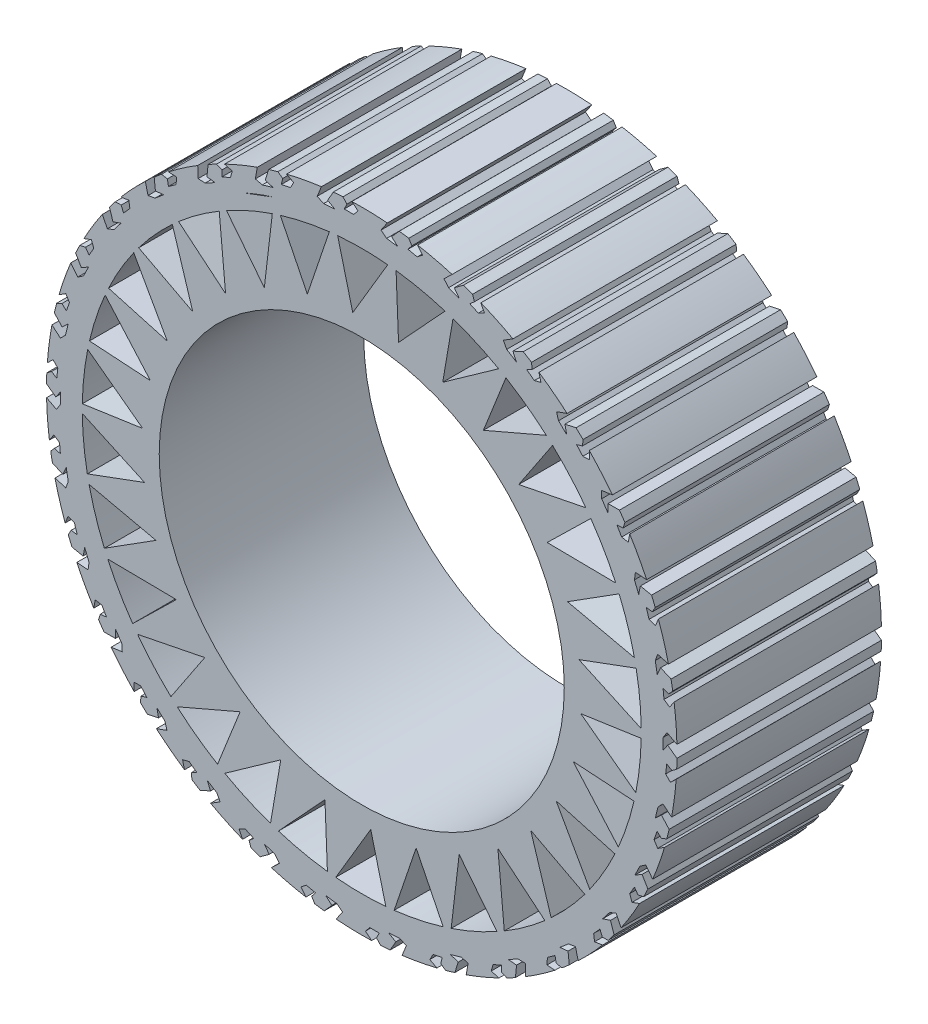
SolidWorks part; units mm, degrees
ref_plane "Front Plane" through (0, 0, 0) normal (0, 0, 1) x (1, 0, 0)
ref_plane "Top Plane" through (0, 0, 0) normal (0, 1, 0) x (1, 0, 0)
ref_plane "Right Plane" through (0, 0, 0) normal (1, 0, 0) x (0, 0, -1)
sketch "Sketch1" plane through (0, 0, 0) normal (0, 0, 1) x (1, 0, 0)
  line L0 (154.9481, 259.0555) -> (145.2899, 265.0606)
  line L1 (-169.385, 140.3878) -> (-194.3847, 220.5688)
  line L2 (-194.8718, 102.1028) -> (-235.9957, 175.334)
  line L3 (-194.8718, 102.1028) -> (-267.2926, 122.4363)
  line L4 (-169.385, 140.3878) -> (-235.9957, 175.334)
  line L5 (-136.4953, 172.5371) -> (-144.278, 256.1637)
  line L6 (-136.4953, 172.5371) -> (-194.3847, 220.5688)
  line L7 (-97.6401, 197.1457) -> (-87.8658, 280.563)
  line L8 (-97.6401, 197.1457) -> (-144.278, 256.1637)
  line L9 (-54.5175, 213.1381) -> (-27.6134, 292.7004)
  line L10 (-54.5175, 213.1381) -> (-87.8658, 280.563)
  line L11 (-9.0123, 219.8153) -> (33.8459, 292.0453)
  line L12 (-9.0123, 219.8153) -> (-27.6134, 292.7004)
  line L13 (36.8869, 216.8856) -> (93.8259, 278.6265)
  line L14 (36.8869, 216.8856) -> (33.8459, 292.0453)
  line L15 (81.1738, 204.4769) -> (149.7053, 253.0303)
  line L16 (81.1738, 204.4769) -> (93.8259, 278.6265)
  line L17 (121.9131, 183.1316) -> (199.0418, 216.3755)
  line L18 (121.9131, 183.1316) -> (149.7053, 253.0303)
  line L19 (157.3243, 153.7826) -> (239.6793, 170.2641)
  line L20 (157.3243, 153.7826) -> (199.0418, 216.3755)
  line L21 (185.8595, 117.7125) -> (269.8416, 116.7113)
  line L22 (185.8595, 117.7125) -> (239.6793, 170.2641)
  line L23 (206.2719, 76.4978) -> (288.2105, 58.0576)
  line L24 (206.2719, 76.4978) -> (269.8416, 116.7113)
  line L25 (217.6691, 31.9398) -> (293.9833, -3.1334)
  line L26 (217.6691, 31.9398) -> (288.2105, 58.0576)
  line L27 (219.5532, -14.0141) -> (286.9076, -64.1875)
  line L28 (219.5532, -14.0141) -> (293.9833, -3.1334)
  line L29 (211.8417, -59.3555) -> (267.2926, -122.4363)
  line L30 (211.8417, -59.3555) -> (286.9076, -64.1875)
  line L31 (194.8718, -102.1028) -> (235.9957, -175.334)
  line L32 (194.8718, -102.1028) -> (267.2926, -122.4363)
  line L33 (169.385, -140.3878) -> (194.3847, -220.5688)
  line L34 (169.385, -140.3878) -> (235.9957, -175.334)
  line L35 (136.4953, -172.5371) -> (144.278, -256.1637)
  line L36 (136.4953, -172.5371) -> (194.3847, -220.5688)
  line L37 (97.6401, -197.1457) -> (87.8658, -280.563)
  line L38 (97.6401, -197.1457) -> (144.278, -256.1637)
  line L39 (54.5175, -213.1381) -> (27.6134, -292.7004)
  line L40 (54.5175, -213.1381) -> (87.8658, -280.563)
  line L41 (9.0123, -219.8153) -> (-33.8459, -292.0453)
  line L42 (9.0123, -219.8153) -> (27.6134, -292.7004)
  line L43 (-36.8869, -216.8856) -> (-93.8259, -278.6265)
  line L44 (-36.8869, -216.8856) -> (-33.8459, -292.0453)
  line L45 (-81.1738, -204.4769) -> (-149.7053, -253.0303)
  line L46 (-81.1738, -204.4769) -> (-93.8259, -278.6265)
  line L47 (-121.9131, -183.1316) -> (-199.0418, -216.3755)
  line L48 (-121.9131, -183.1316) -> (-149.7053, -253.0303)
  line L49 (-157.3243, -153.7826) -> (-239.6793, -170.2641)
  line L50 (-157.3243, -153.7826) -> (-199.0418, -216.3755)
  line L51 (-185.8595, -117.7125) -> (-269.8416, -116.7113)
  line L52 (-185.8595, -117.7125) -> (-239.6793, -170.2641)
  line L53 (-206.2719, -76.4978) -> (-288.2105, -58.0576)
  line L54 (-206.2719, -76.4978) -> (-269.8416, -116.7113)
  line L55 (-217.6691, -31.9398) -> (-293.9833, 3.1334)
  line L56 (-217.6691, -31.9398) -> (-288.2105, -58.0576)
  line L57 (-219.5532, 14.0141) -> (-286.9076, 64.1875)
  line L58 (-219.5532, 14.0141) -> (-293.9833, 3.1334)
  line L59 (-211.8417, 59.3555) -> (-267.2926, 122.4363)
  line L60 (-211.8417, 59.3555) -> (-286.9076, 64.1875)
  line L61 (-118.0669, 269.2512) -> (-87.8658, 280.563)
  line L62 (145.2899, 265.0606) -> (141.9482, 271.3584)
  line L63 (141.9482, 271.3584) -> (151.5132, 277.308)
  line L64 (161.9278, 271.3584) -> (151.5132, 266.6446)
  line L65 (151.5132, 266.6446) -> (154.9481, 259.0555)
  line L67 (170.1652, 266.2702) -> (170.8497, 260.4044)
  line L68 (170.8497, 260.4044) -> (165.433, 257.4571)
  line L69 (165.433, 257.4571) -> (173.0004, 251.8811)
  line L70 (173.0004, 251.8811) -> (179.612, 253.5539)
  line L71 (179.612, 253.5539) -> (177.6416, 261.3416)
  line L72 (228.4039, 210.6697) -> (228.0957, 218.6969)
  line L73 (214.8079, 231.7619) -> (203.6408, 229.3164)
  line L74 (197.2242, 229.0609) -> (195.2649, 235.9159)
  line L75 (205.4228, 221.179) -> (197.2242, 229.0609)
  line L76 (203.6408, 229.3164) -> (205.4228, 221.179)
  line L77 (195.2649, 235.9159) -> (205.8578, 239.7468)
  line L78 (221.8074, 225.0722) -> (221.2573, 219.1923)
  line L79 (221.2573, 219.1923) -> (215.3462, 217.4356)
  line L80 (215.3462, 217.4356) -> (221.589, 210.4081)
  line L81 (221.589, 210.4081) -> (228.4039, 210.6697)
  line L82 (267.2134, 158.5782) -> (268.5809, 166.4941)
  line L83 (258.2998, 182.0363) -> (246.8683, 181.966)
  line L84 (240.5388, 183.0502) -> (240.0475, 190.1627)
  line L85 (246.9195, 173.6359) -> (240.5388, 183.0502)
  line L86 (246.8683, 181.966) -> (246.9195, 173.6359)
  line L87 (240.0475, 190.1627) -> (251.2055, 191.7075)
  line L88 (263.7555, 174.0375) -> (261.995, 168.4005)
  line L89 (261.995, 168.4005) -> (255.8478, 167.9111)
  line L90 (255.8478, 167.9111) -> (260.493, 159.7392)
  line L91 (260.493, 159.7392) -> (267.2134, 158.5782)
  line L92 (294.3444, 99.5561) -> (297.3279, 107.0147)
  line L93 (290.5028, 124.3548) -> (279.3065, 126.6628)
  line L94 (273.3407, 129.0393) -> (274.339, 136.0985)
  line L95 (277.6247, 118.5041) -> (273.3407, 129.0393)
  line L96 (279.3065, 126.6628) -> (277.6247, 118.5041)
  line L97 (274.339, 136.0985) -> (285.5743, 135.2897)
  line L98 (294.1762, 115.3965) -> (291.2822, 110.2487)
  line L99 (291.2822, 110.2487) -> (285.1676, 111.0481)
  line L100 (285.1676, 111.0481) -> (288.0123, 102.089)
  line L101 (288.0123, 102.089) -> (294.3444, 99.5561)
  line L102 (308.6112, 36.183) -> (313.0801, 42.8583)
  line L103 (310.0094, 61.2384) -> (299.5377, 65.8238)
  line L104 (294.1963, 69.3887) -> (296.6405, 76.0861)
  line L105 (296.1963, 58.1931) -> (294.1963, 69.3887)
  line L106 (299.5377, 65.8238) -> (296.1963, 58.1931)
  line L107 (296.6405, 76.0861) -> (307.4622, 72.9591)
  line L108 (311.74, 51.7121) -> (307.839, 47.2785)
  line L109 (307.839, 47.2785) -> (302.0242, 49.3318)
  line L110 (302.0242, 49.3318) -> (302.944, 39.977)
  line L111 (302.944, 39.977) -> (308.6112, 36.183)
  line L112 (309.3901, -28.7716) -> (315.1493, -23.1713)
  line L113 (315.9672, -4.5544) -> (306.6776, 2.108)
  line L114 (302.1942, 6.7055) -> (305.9774, 12.7485)
  line L115 (301.8227, -4.6613) -> (302.1942, 6.7055)
  line L116 (306.6776, 2.108) -> (301.8227, -4.6613)
  line L117 (305.9774, 12.7485) -> (315.9124, 7.4398)
  line L118 (315.6793, -14.2323) -> (310.9417, -17.7579)
  line L119 (310.9417, -17.7579) -> (305.6809, -14.5406)
  line L120 (305.6809, -14.5406) -> (304.6357, -23.8822)
  line L121 (304.6357, -23.8822) -> (309.3901, -28.7716)
  line L122 (296.6473, -92.4687) -> (303.445, -88.1882)
  line L123 (308.1156, -70.1481) -> (300.4142, -61.6999)
  line L124 (296.9847, -56.2707) -> (301.9416, -51.1464)
  line L125 (294.258, -67.3119) -> (296.9847, -56.2707)
  line L126 (300.4142, -61.6999) -> (294.258, -67.3119)
  line L127 (301.9416, -51.1464) -> (310.5558, -58.4047)
  line L128 (305.8219, -79.5547) -> (300.4548, -82.0183)
  line L129 (300.4548, -82.0183) -> (295.9779, -77.7775)
  line L130 (295.9779, -77.7775) -> (293.0132, -86.6977)
  line L131 (293.0132, -86.6977) -> (296.6473, -92.4687)
  line L132 (270.9395, -152.1245) -> (278.4786, -149.3508)
  line L133 (286.7979, -132.6761) -> (281.0213, -122.8112)
  line L134 (278.7955, -116.7876) -> (284.7095, -112.8059)
  line L135 (273.8329, -127.0206) -> (278.7955, -116.7876)
  line L136 (281.0213, -122.8112) -> (273.8329, -127.0206)
  line L137 (284.7095, -112.8059) -> (291.6264, -121.6966)
  line L138 (282.5986, -141.4002) -> (276.8366, -142.6941)
  line L139 (276.8366, -142.6941) -> (273.3392, -137.6151)
  line L140 (273.3392, -137.6151) -> (268.5847, -145.724)
  line L141 (268.5847, -145.724) -> (270.9395, -152.1245)
  line L142 (233.3904, -205.1317) -> (241.3414, -203.9861)
  line L143 (252.9458, -189.4054) -> (249.3464, -178.5551)
  line L144 (248.4216, -172.2004) -> (255.0342, -169.5353)
  line L145 (241.4399, -181.178) -> (248.4216, -172.2004)
  line L146 (249.3464, -178.5551) -> (241.4399, -181.178)
  line L147 (255.0342, -169.5353) -> (259.9515, -179.6698)
  line L148 (247.0244, -197.0658) -> (241.1193, -197.1334)
  line L149 (241.1193, -197.1334) -> (238.7543, -191.4383)
  line L150 (238.7543, -191.4383) -> (232.4178, -198.3815)
  line L151 (232.4178, -198.3815) -> (233.3904, -205.1317)
  line L152 (185.6409, -249.1736) -> (193.6564, -249.7062)
  line L153 (208.0387, -237.8569) -> (206.7739, -226.4953)
  line L154 (207.1905, -220.0871) -> (214.2128, -218.8551)
  line L155 (198.4948, -227.417) -> (207.1905, -220.0871)
  line L156 (206.7739, -226.4953) -> (198.4948, -227.417)
  line L157 (214.2128, -218.8551) -> (216.9155, -229.7905)
  line L158 (200.654, -244.1187) -> (194.8639, -242.9571)
  line L159 (194.8639, -242.9571) -> (193.7347, -236.8947)
  line L160 (193.7347, -236.8947) -> (186.0931, -242.3687)
  line L161 (186.0931, -242.3687) -> (185.6409, -249.1736)
  line L162 (129.7781, -282.3255) -> (137.5077, -284.513)
  line L163 (154.0394, -275.9128) -> (155.1644, -264.5366)
  line L164 (156.9042, -258.3551) -> (164.0292, -258.6099)
  line L165 (146.8746, -263.7168) -> (156.9042, -258.3551)
  line L166 (155.1644, -264.5366) -> (146.8746, -263.7168)
  line L167 (164.0292, -258.6099) -> (164.3992, -269.8683)
  line L168 (145.5141, -280.5025) -> (140.092, -278.1624)
  line L169 (140.092, -278.1624) -> (140.2479, -271.9977)
  line L170 (140.2479, -271.9977) -> (131.6352, -275.7633)
  line L171 (131.6352, -275.7633) -> (129.7781, -282.3255)
  line L172 (68.2434, -303.1384) -> (75.3493, -306.8851)
  line L173 (93.3077, -301.91) -> (96.7734, -291.0163)
  line L174 (99.7605, -285.3316) -> (106.6767, -287.0623)
  line L175 (88.8352, -288.4909) -> (99.7605, -285.3316)
  line L176 (96.7734, -291.0163) -> (88.8352, -288.4909)
  line L177 (106.6767, -287.0623) -> (104.6979, -298.1515)
  line L178 (84.0146, -304.6269) -> (79.1975, -301.2106)
  line L179 (79.1975, -301.2106) -> (80.6317, -295.2131)
  line L180 (80.6317, -295.2131) -> (71.4243, -297.1057)
  line L181 (71.4243, -297.1057) -> (68.2434, -303.1384)
  line L182 (3.7261, -310.7027) -> (9.8977, -315.845)
  line L183 (28.4981, -314.7123) -> (34.153, -304.7772)
  line L184 (38.2567, -299.8378) -> (44.662, -302.9686)
  line L185 (26.9133, -300.6565) -> (38.2567, -299.8378)
  line L186 (34.153, -304.7772) -> (26.9133, -300.6565)
  line L187 (44.662, -302.9686) -> (40.4208, -313.4041)
  line L188 (18.8431, -315.4377) -> (14.8416, -311.0946)
  line L189 (14.8416, -311.0946) -> (17.4914, -305.5263)
  line L190 (17.4914, -305.5263) -> (8.0917, -305.4632)
  line L191 (8.0917, -305.4632) -> (3.7261, -310.7027)
  line L192 (-60.9541, -304.6878) -> (-55.9865, -311.0008)
  line L193 (-37.557, -313.7602) -> (-29.9601, -305.2179)
  line L194 (-24.9191, -301.2396) -> (-19.3047, -305.6338)
  line L195 (-36.1848, -299.6821) -> (-24.9191, -301.2396)
  line L196 (-29.9601, -305.2179) -> (-36.1848, -299.6821)
  line L197 (-19.3047, -305.6338) -> (-25.6228, -314.9595)
  line L198 (-47.1518, -312.4623) -> (-50.1629, -307.3821)
  line L199 (-50.1629, -307.3821) -> (-46.4133, -302.4864)
  line L200 (-46.4133, -302.4864) -> (-55.5945, -300.4705)
  line L201 (-55.5945, -300.4705) -> (-60.9541, -304.6878)
  line L202 (-122.9702, -285.3566) -> (-119.4237, -292.5645)
  line L203 (-101.9707, -299.0953) -> (-92.7637, -292.3191)
  line L204 (-87.0058, -289.4759) -> (-82.4277, -294.9413)
  line L205 (-97.7015, -285.6101) -> (-87.0058, -289.4759)
  line L206 (-92.7637, -292.3191) -> (-97.7015, -285.6101)
  line L207 (-82.4277, -294.9413) -> (-90.5467, -302.7496)
  line L208 (-111.086, -295.8309) -> (-112.9751, -290.2356)
  line L209 (-112.9751, -290.2356) -> (-108.2895, -286.2265)
  line L210 (-108.2895, -286.2265) -> (-116.8509, -282.3457)
  line L211 (-116.8509, -282.3457) -> (-122.9702, -285.3566)
  line L212 (-179.612, -253.5539) -> (-177.6416, -261.3416)
  line L213 (-161.9278, -271.3584) -> (-151.5132, -266.6446)
  line L214 (-145.2899, -265.0606) -> (-141.9482, -271.3584)
  line L215 (-154.9481, -259.0555) -> (-145.2899, -265.0606)
  line L216 (-151.5132, -266.6446) -> (-154.9481, -259.0555)
  line L217 (-141.9482, -271.3584) -> (-151.5132, -277.308)
  line L218 (-170.1652, -266.2702) -> (-170.8497, -260.4044)
  line L219 (-170.8497, -260.4044) -> (-165.433, -257.4571)
  line L220 (-165.433, -257.4571) -> (-173.0004, -251.8811)
  line L221 (-173.0004, -251.8811) -> (-179.612, -253.5539)
  line L222 (-228.4039, -210.6697) -> (-228.0957, -218.6969)
  line L223 (-214.8079, -231.7619) -> (-203.6408, -229.3164)
  line L224 (-197.2242, -229.0609) -> (-195.2649, -235.9159)
  line L225 (-205.4228, -221.179) -> (-197.2242, -229.0609)
  line L226 (-203.6408, -229.3164) -> (-205.4228, -221.179)
  line L227 (-195.2649, -235.9159) -> (-205.8578, -239.7468)
  line L228 (-221.8074, -225.0722) -> (-221.2573, -219.1923)
  line L229 (-221.2573, -219.1923) -> (-215.3462, -217.4356)
  line L230 (-215.3462, -217.4356) -> (-221.589, -210.4081)
  line L231 (-221.589, -210.4081) -> (-228.4039, -210.6697)
  line L232 (-267.2134, -158.5782) -> (-268.5809, -166.4941)
  line L233 (-258.2998, -182.0363) -> (-246.8683, -181.966)
  line L234 (-240.5388, -183.0502) -> (-240.0475, -190.1627)
  line L235 (-246.9195, -173.6359) -> (-240.5388, -183.0502)
  line L236 (-246.8683, -181.966) -> (-246.9195, -173.6359)
  line L237 (-240.0475, -190.1627) -> (-251.2055, -191.7075)
  line L238 (-263.7555, -174.0375) -> (-261.995, -168.4005)
  line L239 (-261.995, -168.4005) -> (-255.8478, -167.9111)
  line L240 (-255.8478, -167.9111) -> (-260.493, -159.7392)
  line L241 (-260.493, -159.7392) -> (-267.2134, -158.5782)
  line L242 (-294.3444, -99.5561) -> (-297.3279, -107.0147)
  line L243 (-290.5028, -124.3548) -> (-279.3065, -126.6628)
  line L244 (-273.3407, -129.0393) -> (-274.339, -136.0985)
  line L245 (-277.6247, -118.5041) -> (-273.3407, -129.0393)
  line L246 (-279.3065, -126.6628) -> (-277.6247, -118.5041)
  line L247 (-274.339, -136.0985) -> (-285.5743, -135.2897)
  line L248 (-294.1762, -115.3965) -> (-291.2822, -110.2487)
  line L249 (-291.2822, -110.2487) -> (-285.1676, -111.0481)
  line L250 (-285.1676, -111.0481) -> (-288.0123, -102.089)
  line L251 (-288.0123, -102.089) -> (-294.3444, -99.5561)
  line L252 (-308.6112, -36.183) -> (-313.0801, -42.8583)
  line L253 (-310.0094, -61.2384) -> (-299.5377, -65.8238)
  line L254 (-294.1963, -69.3887) -> (-296.6405, -76.0861)
  line L255 (-296.1963, -58.1931) -> (-294.1963, -69.3887)
  line L256 (-299.5377, -65.8238) -> (-296.1963, -58.1931)
  line L257 (-296.6405, -76.0861) -> (-307.4622, -72.9591)
  line L258 (-311.74, -51.7121) -> (-307.839, -47.2785)
  line L259 (-307.839, -47.2785) -> (-302.0242, -49.3318)
  line L260 (-302.0242, -49.3318) -> (-302.944, -39.977)
  line L261 (-302.944, -39.977) -> (-308.6112, -36.183)
  line L262 (-309.3901, 28.7716) -> (-315.1493, 23.1713)
  line L263 (-315.9672, 4.5544) -> (-306.6776, -2.108)
  line L264 (-302.1942, -6.7055) -> (-305.9774, -12.7485)
  line L265 (-301.8227, 4.6613) -> (-302.1942, -6.7055)
  line L266 (-306.6776, -2.108) -> (-301.8227, 4.6613)
  line L267 (-305.9774, -12.7485) -> (-315.9124, -7.4398)
  line L268 (-315.6793, 14.2323) -> (-310.9417, 17.7579)
  line L269 (-310.9417, 17.7579) -> (-305.6809, 14.5406)
  line L270 (-305.6809, 14.5406) -> (-304.6357, 23.8822)
  line L271 (-304.6357, 23.8822) -> (-309.3901, 28.7716)
  line L272 (-296.6473, 92.4687) -> (-303.445, 88.1882)
  line L273 (-308.1156, 70.1481) -> (-300.4142, 61.6999)
  line L274 (-296.9847, 56.2707) -> (-301.9416, 51.1464)
  line L275 (-294.258, 67.3119) -> (-296.9847, 56.2707)
  line L276 (-300.4142, 61.6999) -> (-294.258, 67.3119)
  line L277 (-301.9416, 51.1464) -> (-310.5558, 58.4047)
  line L278 (-305.8219, 79.5547) -> (-300.4548, 82.0183)
  line L279 (-300.4548, 82.0183) -> (-295.9779, 77.7775)
  line L280 (-295.9779, 77.7775) -> (-293.0132, 86.6977)
  line L281 (-293.0132, 86.6977) -> (-296.6473, 92.4687)
  line L282 (-270.9395, 152.1245) -> (-278.4786, 149.3508)
  line L283 (-286.7979, 132.6761) -> (-281.0213, 122.8112)
  line L284 (-278.7955, 116.7876) -> (-284.7095, 112.8059)
  line L285 (-273.8329, 127.0206) -> (-278.7955, 116.7876)
  line L286 (-281.0213, 122.8112) -> (-273.8329, 127.0206)
  line L287 (-284.7095, 112.8059) -> (-291.6264, 121.6966)
  line L288 (-282.5986, 141.4002) -> (-276.8366, 142.6941)
  line L289 (-276.8366, 142.6941) -> (-273.3392, 137.6151)
  line L290 (-273.3392, 137.6151) -> (-268.5847, 145.724)
  line L291 (-268.5847, 145.724) -> (-270.9395, 152.1245)
  line L292 (-233.3904, 205.1317) -> (-241.3414, 203.9861)
  line L293 (-252.9458, 189.4054) -> (-249.3464, 178.5551)
  line L294 (-248.4216, 172.2004) -> (-255.0342, 169.5353)
  line L295 (-241.4399, 181.178) -> (-248.4216, 172.2004)
  line L296 (-249.3464, 178.5551) -> (-241.4399, 181.178)
  line L297 (-255.0342, 169.5353) -> (-259.9515, 179.6698)
  line L298 (-247.0244, 197.0658) -> (-241.1193, 197.1334)
  line L299 (-241.1193, 197.1334) -> (-238.7543, 191.4383)
  line L300 (-238.7543, 191.4383) -> (-232.4178, 198.3815)
  line L301 (-232.4178, 198.3815) -> (-233.3904, 205.1317)
  line L302 (-185.6409, 249.1736) -> (-193.6564, 249.7062)
  line L303 (-208.0387, 237.8569) -> (-206.7739, 226.4953)
  line L304 (-207.1905, 220.0871) -> (-214.2128, 218.8551)
  line L305 (-198.4948, 227.417) -> (-207.1905, 220.0871)
  line L306 (-206.7739, 226.4953) -> (-198.4948, 227.417)
  line L307 (-214.2128, 218.8551) -> (-216.9155, 229.7905)
  line L308 (-200.654, 244.1187) -> (-194.8639, 242.9571)
  line L309 (-194.8639, 242.9571) -> (-193.7347, 236.8947)
  line L310 (-193.7347, 236.8947) -> (-186.0931, 242.3687)
  line L311 (-186.0931, 242.3687) -> (-185.6409, 249.1736)
  line L312 (-129.7781, 282.3255) -> (-137.5077, 284.513)
  line L313 (-154.0394, 275.9128) -> (-155.1644, 264.5366)
  line L314 (-156.9042, 258.3551) -> (-164.0292, 258.6099)
  line L315 (-146.8746, 263.7168) -> (-156.9042, 258.3551)
  line L316 (-155.1644, 264.5366) -> (-146.8746, 263.7168)
  line L317 (-164.0292, 258.6099) -> (-164.3992, 269.8683)
  line L318 (-145.5141, 280.5025) -> (-140.092, 278.1624)
  line L319 (-140.092, 278.1624) -> (-140.2479, 271.9977)
  line L320 (-140.2479, 271.9977) -> (-131.6352, 275.7633)
  line L321 (-131.6352, 275.7633) -> (-129.7781, 282.3255)
  line L322 (-68.2434, 303.1384) -> (-75.3493, 306.8851)
  line L323 (-93.3077, 301.91) -> (-96.7734, 291.0163)
  line L324 (-99.7605, 285.3316) -> (-106.6767, 287.0623)
  line L325 (-88.8352, 288.4909) -> (-99.7605, 285.3316)
  line L326 (-96.7734, 291.0163) -> (-88.8352, 288.4909)
  line L327 (-106.6767, 287.0623) -> (-104.6979, 298.1515)
  line L328 (-84.0146, 304.6269) -> (-79.1975, 301.2106)
  line L329 (-79.1975, 301.2106) -> (-80.6317, 295.2131)
  line L330 (-80.6317, 295.2131) -> (-71.4243, 297.1057)
  line L331 (-71.4243, 297.1057) -> (-68.2434, 303.1384)
  line L332 (-3.7261, 310.7027) -> (-9.8977, 315.845)
  line L333 (-28.4981, 314.7123) -> (-34.153, 304.7772)
  line L334 (-38.2567, 299.8378) -> (-44.662, 302.9686)
  line L335 (-26.9133, 300.6565) -> (-38.2567, 299.8378)
  line L336 (-34.153, 304.7772) -> (-26.9133, 300.6565)
  line L337 (-44.662, 302.9686) -> (-40.4208, 313.4041)
  line L338 (-18.8431, 315.4377) -> (-14.8416, 311.0946)
  line L339 (-14.8416, 311.0946) -> (-17.4914, 305.5263)
  line L340 (-17.4914, 305.5263) -> (-8.0917, 305.4632)
  line L341 (-8.0917, 305.4632) -> (-3.7261, 310.7027)
  line L342 (60.9541, 304.6878) -> (55.9865, 311.0008)
  line L343 (37.557, 313.7602) -> (29.9601, 305.2179)
  line L344 (24.9191, 301.2396) -> (19.3047, 305.6338)
  line L345 (36.1848, 299.6821) -> (24.9191, 301.2396)
  line L346 (29.9601, 305.2179) -> (36.1848, 299.6821)
  line L347 (19.3047, 305.6338) -> (25.6228, 314.9595)
  line L348 (47.1518, 312.4623) -> (50.1629, 307.3821)
  line L349 (50.1629, 307.3821) -> (46.4133, 302.4864)
  line L350 (46.4133, 302.4864) -> (55.5945, 300.4705)
  line L351 (55.5945, 300.4705) -> (60.9541, 304.6878)
  line L352 (122.9702, 285.3566) -> (119.4237, 292.5645)
  line L353 (101.9707, 299.0953) -> (92.7637, 292.3191)
  line L354 (87.0058, 289.4759) -> (82.4277, 294.9413)
  line L355 (97.7015, 285.6101) -> (87.0058, 289.4759)
  line L356 (92.7637, 292.3191) -> (97.7015, 285.6101)
  line L357 (82.4277, 294.9413) -> (90.5467, 302.7496)
  line L358 (111.086, 295.8309) -> (112.9751, 290.2356)
  line L359 (112.9751, 290.2356) -> (108.2895, 286.2265)
  line L360 (108.2895, 286.2265) -> (116.8509, 282.3457)
  line L361 (116.8509, 282.3457) -> (122.9702, 285.3566)
  circle A0 centre (0, 0) radius 316
  circle A1 centre (0, 0) radius 203
  circle A2 centre (0, 0) radius 220
  circle A3 centre (0, 0) radius 294
  circle A4 centre (0, 0) radius 280.1501
  circle A5 centre (0, 0) radius 316
  circle A6 centre (0, 0) radius 316
  circle A7 centre (0, 0) radius 316
  circle A8 centre (0, 0) radius 316
  circle A9 centre (0, 0) radius 316
  circle A10 centre (0, 0) radius 316
  circle A11 centre (0, 0) radius 316
  circle A12 centre (0, 0) radius 316
  circle A13 centre (0, 0) radius 316
  circle A14 centre (0, 0) radius 316
  circle A15 centre (0, 0) radius 316
  circle A16 centre (0, 0) radius 316
  circle A17 centre (0, 0) radius 316
  circle A18 centre (0, 0) radius 316
  circle A19 centre (0, 0) radius 316
  circle A20 centre (0, 0) radius 316
  circle A21 centre (0, 0) radius 316
  circle A22 centre (0, 0) radius 316
  circle A23 centre (0, 0) radius 316
  circle A24 centre (0, 0) radius 316
  circle A25 centre (0, 0) radius 316
  circle A26 centre (0, 0) radius 316
  circle A27 centre (0, 0) radius 316
  circle A28 centre (0, 0) radius 316
  circle A29 centre (0, 0) radius 316
  circle A30 centre (0, 0) radius 316
  circle A31 centre (0, 0) radius 316
  circle A32 centre (0, 0) radius 316
  circle A33 centre (0, 0) radius 316
  point P100 (0, 0)
  point P461 (0, 0)
  dimension "D1" = 406
  dimension "D2" = 632
  dimension "D3" = 440
  dimension "D4" = 588
  dimension "D5" = 45
  dimension "D6" = 30
  dimension "D7" = 30
extrude "Boss-Extrude5" add sketch "Sketch1" along normal blind 205 contours A2 A1 | L24 A4 L21 A2 | L22 A4 L19 A2 | L20 A4 L17 A2 | L18 A4 L15 A2 | L16 A4 L13 A2 | L14 A4 L11 A2 | L12 A4 L9 A2 | L10 A4 L7 A2 | L8 A4 L5 A2 | L6 A4 L1 A2 | L4 A4 L2 A2 | L3 A4 L59 A2 | L60 A4 L57 A2 | L58 A4 L55 A2 | L56 A4 L53 A2 | L54 A4 L51 A2 | L52 A4 L49 A2 | L50 A4 L47 A2 | L48 A4 L45 A2 | L46 A4 L43 A2 | L44 A4 L41 A2 | L42 A4 L39 A2 | L40 A4 L37 A2 | L38 A4 L35 A2 | L36 A4 L33 A2 | L34 A4 L31 A2 | L32 A4 L29 A2 | L30 A4 L27 A2 | L28 A4 L25 A2 | L26 A4 L23 A2 | A0 A3 | A4 L25 A3 L26 | A4 L23 A3 L24 | A4 L21 A3 L22 | A4 L19 A3 L20 | A4 L27 A3 L28 | A4 L29 A3 L30 | A4 L33 A3 L34 | A4 L35 A3 L36 | A4 L31 A3 L32 | A4 L30 L27 | A4 L32 L29 | A4 L34 L31 | A4 L36 L33 | A4 L38 L35 | A4 L37 A3 L38 | A4 L40 L37 | A4 L39 A3 L40 | A4 L28 L25 | A4 L26 L23 | A4 L24 L21 | A4 L17 A3 L18 | A4 L15 A3 L16 | A4 L13 A3 L14 | A4 L11 A3 L12 | A4 L14 L11 | A4 L16 L13 | A4 L18 L15 | A4 L22 L19 | A4 L20 L17 | A4 L41 A3 L42 | A4 L43 A3 L44 | A4 L45 A3 L46 | A4 L46 L43 | A4 L44 L41 | A4 L42 L39 | A4 L51 A3 L52 | A4 L49 A3 L50 | A4 L47 A3 L48 | A4 L48 L45 | A4 L50 L47 | A4 L52 L49 | A4 L54 L51 | A4 L53 A3 L54 | A4 L57 A3 L58 | A4 L55 A3 L56 | A4 L56 L53 | A4 L58 L55 | A4 L59 A3 L60 | A4 L2 A3 L3 | A4 L1 A3 L4 | A4 L5 A3 L6 | A4 L7 L61 A3 L8 | A4 L9 A3 L10 | A4 L60 L57 | A4 L3 L59 | A4 L12 L9 | A4 L10 L7 | A4 L8 L5 | A4 L6 L1 | A4 L4 L2 region at (145.0885, 259.1648, 0) region at (-199.4371, 138.6263, 0) region at (-166.2569, 177.0623, 0) region at (-149.4329, 152.8744, 0) region at (-211.7704, 193.4845, 0) region at (-189.2811, 212.7435, 0) region at (-229.3767, 168.7408, 0) region at (-125.8104, 207.7598, 0) region at (-223.901, 94.1317, 0) region at (-166.9151, 233.2859, 0) region at (-247.3704, 145.2268, 0) region at (-140.913, 247.4483, 0) region at (-79.8655, 229.3772, 0) region at (-259.4475, 117.3633, 0) region at (-238.5793, 45.5231, 0) region at (-114.9107, 262.7401, 0) region at (-272.1591, 90.622, 0) region at (-86.3863, 271.3385, 0) region at (-30.43, 240.9698, 0) region at (-278.1791, 60.8565, 0) region at (-242.8305, -5.0751, 0) region at (-285.0532, 32.0567, 0) region at (-57.5986, 281.0077, 0) region at (-28.0841, 283.3698, 0) region at (20.3354, 242.0308, 0) region at (-284.753, 1.6899, 0) region at (-236.4689, -55.4515, 0) region at (-285.489, -27.9097, 0) region at (2.0849, 286.8425, 0) region at (31.4455, 283.0165, 0) region at (70.212, 232.5138, 0) region at (-278.8819, -57.5505, 0) region at (-219.7725, -103.4044, 0) region at (-273.4477, -86.6563, 0) region at (61.6772, 280.1408, 0) region at (89.6007, 270.294, 0) region at (117.0201, 212.835, 0) region at (-260.8222, -114.2757, 0) region at (-193.4709, -146.8381, 0) region at (-249.4553, -141.6157, 0) region at (118.574, 261.1956, 0) region at (143.84, 245.7584, 0) region at (158.7138, 183.8542, 0) region at (-231.3634, -166.0065, 0) region at (-158.7138, -183.8542, 0) region at (-214.5606, -190.3857, 0) region at (170.2885, 230.835, 0) region at (191.7928, 210.482, 0) region at (193.4709, 146.8381, 0) region at (-191.7928, -210.482, 0) region at (-117.0201, -212.835, 0) region at (-170.2885, -230.835, 0) region at (214.5606, 190.3857, 0) region at (231.3634, 166.0065, 0) region at (219.7725, 103.4044, 0) region at (-143.84, -245.7584, 0) region at (-70.212, -232.5138, 0) region at (-118.574, -261.1956, 0) region at (249.4553, 141.6157, 0) region at (260.8222, 114.2757, 0)
